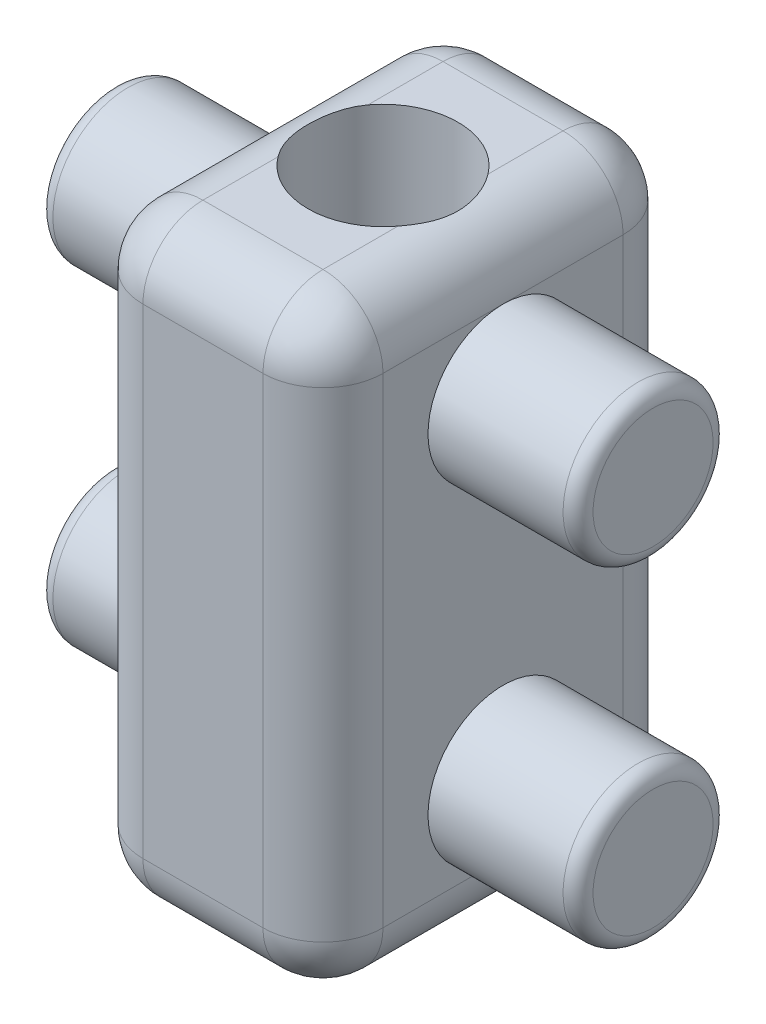
SolidWorks part; units mm, degrees
ref_plane "Front Plane" through (0, 0, 0) normal (0, 0, 1) x (1, 0, 0)
ref_plane "Top Plane" through (0, 0, 0) normal (0, 1, 0) x (1, 0, 0)
ref_plane "Right Plane" through (0, 0, 0) normal (1, 0, 0) x (0, 0, -1)
sketch "Sketch1" plane through (0, 0, 0) normal (1, 0, 0) x (0, 0, -1)
  line L1 (-7.62, -12.7) -> (7.62, -12.7)
  line L2 (-7.62, -12.7) -> (-7.62, 12.7)
  line L3 (-7.62, 12.7) -> (7.62, 12.7)
  line L4 (7.62, -12.7) -> (7.62, 12.7)
  line L5 (-7.62, -12.7) -> (7.62, 12.7) construction
  line L6 (-7.62, 12.7) -> (7.62, -12.7) construction
  point P0 (0, 0)
  dimension "D1" = 25.4
  dimension "D2" = 15.24
extrude "Boss-Extrude1" add sketch "Sketch1" along normal mid plane 10.16
fillet "Fillet1" radius 2.54 12 edges at (0, -12.7, -7.62) (0, 12.7, -7.62) (0, 12.7, 7.62) (0, -12.7, 7.62) (-5.08, 12.7, 0) (-5.08, 0, 7.62) (-5.08, -12.7, 0) (-5.08, 0, -7.62) (5.08, -12.7, 0) (5.08, 0, 7.62) (5.08, 12.7, 0) (5.08, 0, -7.62)
sketch "Sketch2" plane through (5.08, 0, 0) normal (1, 0, 0) x (0, 0, -1)
  line L0 (0, 6.985) -> (0, -6.985) construction
  circle A0 centre (0, 6.985) radius 3.175
  circle A1 centre (0, -6.985) radius 3.175
  point P3 (0, 0)
  dimension "D2" = 6.35
  dimension "D1" = 13.97
extrude "Boss-Extrude2" add sketch "Sketch2" along normal blind 6.35
mirror "Mirror1" about plane through (0, 0, 0) normal (1, 0, 0) of "Boss-Extrude2"
sketch "Sketch3" plane through (0, 12.7, 0) normal (0, 1, 0) x (1, 0, 0)
  line L0 (2.54, 5.08) -> (-2.54, 5.08) construction
  line L1 (-2.54, 5.08) -> (2.54, 5.08)
  line L2 (-2.54, 5.08) -> (-2.54, -5.08)
  line L3 (-2.54, -5.08) -> (2.54, -5.08)
  line L4 (2.54, 5.08) -> (2.54, -5.08)
  line L5 (-2.54, 5.08) -> (-2.54, -5.08) construction
extrude "Boss-Extrude3" add sketch "Sketch3" along normal blind 5.08
sketch "Sketch4" plane through (0, 17.78, 0) normal (0, 1, 0) x (1, 0, 0)
  line L0 (2.54, 5.08) -> (-2.54, 5.08) construction
  line L1 (-3.81, -6.35) -> (3.81, -6.35)
  line L2 (-3.81, -6.35) -> (-3.81, 6.35)
  line L3 (-3.81, 6.35) -> (3.81, 6.35)
  line L4 (3.81, -6.35) -> (3.81, 6.35)
  line L5 (-3.81, -6.35) -> (3.81, 6.35) construction
  line L6 (-3.81, 6.35) -> (3.81, -6.35) construction
  line L7 (2.54, -5.08) -> (2.54, 5.08) construction
  point P0 (0, 0)
  dimension "D1" = 1.27
  dimension "D2" = 1.27
extrude "Boss-Extrude4" add sketch "Sketch4" along normal blind 25.4
fillet "Fillet2" radius 2.54 2 edges at (0, 17.78, -6.35) (0, 17.78, 6.35)
fillet "Fillet3" radius 3.81 4 edges at (0, 43.18, 6.35) (-3.81, 43.18, 0) (0, 43.18, -6.35) (3.81, 43.18, 0)
sketch "Sketch5" plane through (0, 0, -6.35) normal (0, 0, -1) x (-1, 0, 0)
  line L0 (0, 39.37) -> (0, 25.4) construction
  line L1 (3.81, 39.37) -> (-3.81, 39.37) construction
  circle A0 centre (0, 32.385) radius 1.905
  circle A1 centre (0, 25.4) radius 1.905
  dimension "D2" = 3.81
  dimension "D1" = 13.97
extrude "Boss-Extrude5" add sketch "Sketch5" along normal blind 1.27
ref_plane "Plane1" through (0, 21.59, 0) normal (0, 1, 0) x (1, 0, 0)
sketch "Sketch6" plane through (0, 21.59, 0) normal (0, 1, 0) x (1, 0, 0)
  line L0 (-3.81, 8.763) -> (3.81, 8.763) construction
  line L1 (-3.81, 10.541) -> (3.81, 10.541)
  line L2 (-3.81, 6.985) -> (3.81, 6.985)
  line L3 (1.905, 7.62) -> (-1.905, 7.62) construction
  arc A0 (-3.81, 10.541) -> (-3.81, 6.985) centre (-3.81, 8.763) ccw
  arc A1 (3.81, 6.985) -> (3.81, 10.541) centre (3.81, 8.763) ccw
  point P2 (0, 8.763)
  dimension "D1" = 3.556
  dimension "D2" = 7.62
  dimension "D3" = 0.635
extrude "Boss-Extrude6" add sketch "Sketch6" along normal blind 25.4
fillet "Fillet4" radius 1.27 8 edges at (0, 21.59, -6.985) (5.588, 21.59, -8.763) (0, 21.59, -10.541) (-5.588, 21.59, -8.763) (0, 46.99, -10.541) (5.588, 46.99, -8.763) (0, 46.99, -6.985) (-5.588, 46.99, -8.763)
sketch "Sketch7" plane through (0, 0, -10.541) normal (0, 0, -1) x (-1, 0, 0)
  line L0 (3.81, 45.72) -> (-3.81, 45.72) construction
  line L1 (-2.794, 23.495) -> (2.794, 23.495)
  line L2 (-2.794, 23.495) -> (-2.794, 45.085)
  line L3 (-2.794, 45.085) -> (2.794, 45.085)
  line L4 (2.794, 23.495) -> (2.794, 45.085)
  line L5 (-2.794, 23.495) -> (2.794, 45.085) construction
  line L6 (-2.794, 45.085) -> (2.794, 23.495) construction
  line L8 (3.81, 45.72) -> (3.81, 22.86) construction
  line L9 (-3.81, 22.86) -> (3.81, 22.86) construction
  point P0 (0, 34.29)
  dimension "D1" = 0.635
  dimension "D2" = 1.016
  dimension "D3" = 0.635
extrude "Cut-Extrude1" cut sketch "Sketch7" against normal blind 1.016
fillet "Fillet5" radius 0.254 4 edges at (0, 23.495, -10.541) (-2.794, 34.29, -10.541) (2.794, 34.29, -10.541) (0, 45.085, -10.541)
sketch "Sketch8" plane through (3.81, 0, 0) normal (1, 0, 0) x (0, 0, -1)
  line L0 (6.35, 39.37) -> (-6.35, 39.37) construction
  circle A0 centre (0, 33.02) radius 4.445
  point P2 (0, 39.37)
  dimension "D1" = 8.89
  dimension "D2" = 6.35
extrude "Cut-Extrude2" cut sketch "Sketch8" against normal up to next
fillet "Fillet6" radius 0.635 4 edges at (-11.43, -6.985, -3.175) (-11.43, 6.985, -3.175) (11.43, -6.985, -3.175) (11.43, 6.985, -3.175)
sketch "Sketch9" plane through (11.43, 0, 0) normal (1, 0, 0) x (0, 0, -1)
  line L0 (-5.08, 12.7) -> (5.08, 12.7) construction
  line L1 (12.7, 63.5) -> (-12.7, 63.5)
  line L2 (12.7, 63.5) -> (12.7, 12.7)
  line L3 (12.7, 12.7) -> (-12.7, 12.7)
  line L4 (-12.7, 63.5) -> (-12.7, 12.7)
  point P6 (0, 12.7)
  dimension "D1" = 25.4
  dimension "D2" = 50.8
extrude "Cut-Extrude3" cut sketch "Sketch9" against normal blind 22.86
sketch "Sketch10" plane through (0, 12.7, 0) normal (0, 1, 0) x (1, 0, 0)
  circle A0 centre (0, 0) radius 3.175
  dimension "D1" = 6.35
extrude "Cut-Extrude4" cut sketch "Sketch10" against normal blind 12.7
